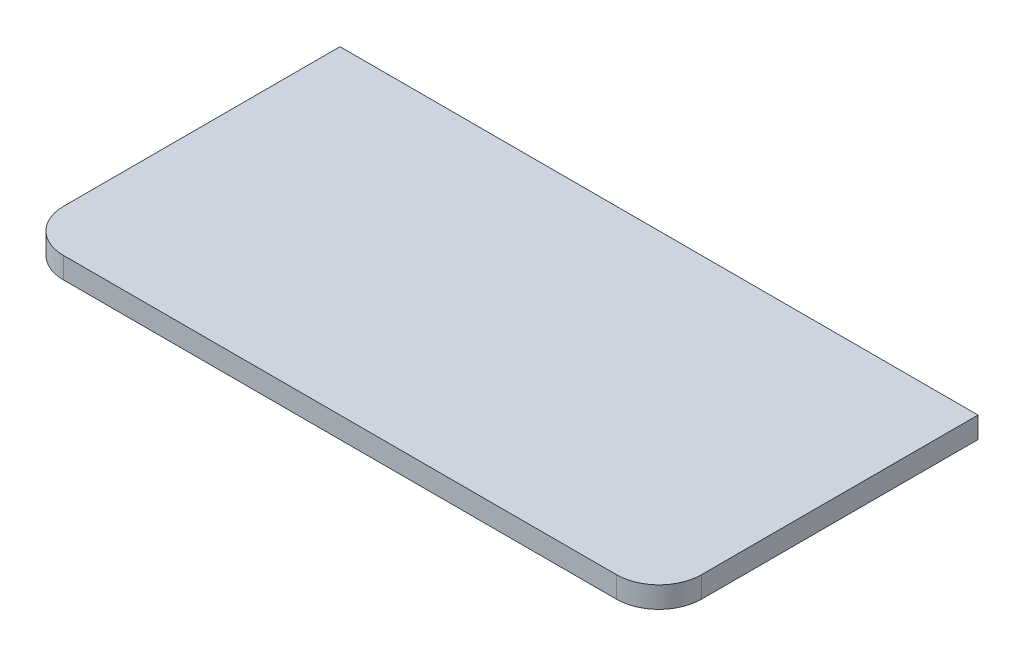
SolidWorks part; units mm, degrees
ref_plane "Ebene vorne" through (0, 0, 0) normal (0, 0, 1) x (1, 0, 0)
ref_plane "Ebene oben" through (0, 0, 0) normal (0, 1, 0) x (1, 0, 0)
ref_plane "Ebene rechts" through (0, 0, 0) normal (1, 0, 0) x (0, 0, -1)
sketch "Skizze1" plane through (0, 0, 0) normal (0, 1, 0) x (1, 0, 0)
  line L1 (0, -75) -> (150, -75)
  line L2 (0, -75) -> (0, 75)
  line L3 (0, 75) -> (150, 75)
  line L4 (150, -75) -> (150, 75)
  line L6 (0, 0) -> (150, 0) construction
  dimension "D1" = 150
extrude "Linear austragen1" add sketch "Skizze1" along normal blind 10
fillet "Verrundung1" radius 20 1 edges at (150, 5, 75)
mirror "Spiegeln2" about plane through (0, 10, 75) normal (1, 0, 0) of "Verrundung1", "Linear austragen1"
